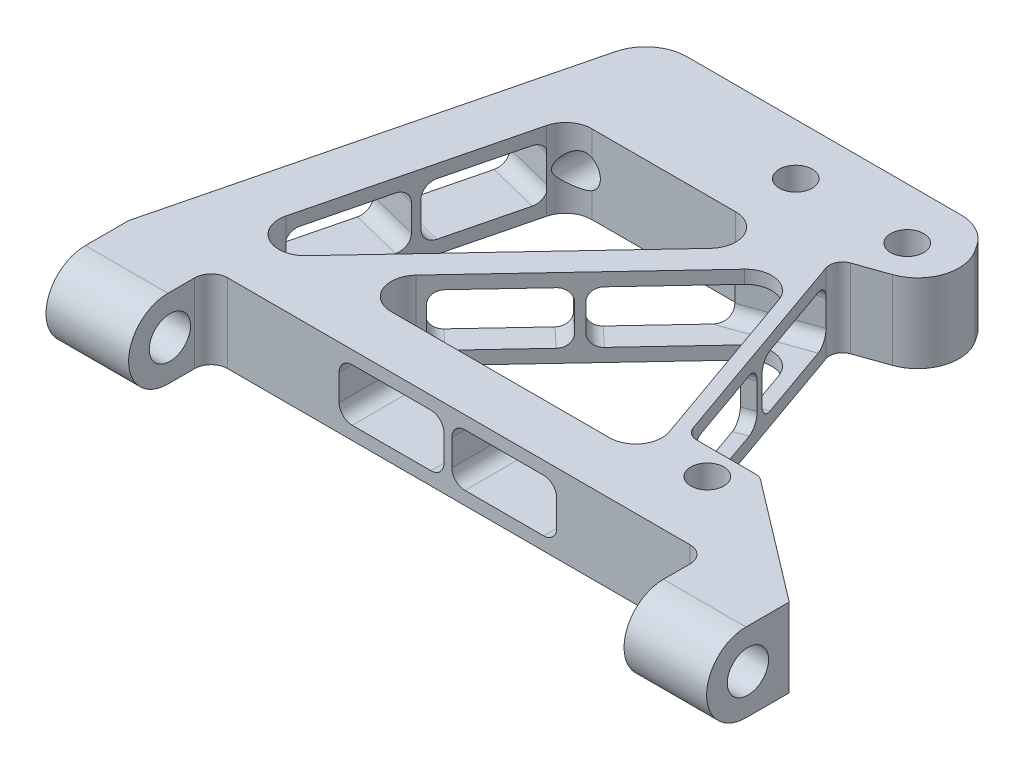
SolidWorks part; units mm, degrees
material "6061-T6 (SS)"
ref_plane "Front Plane" through (0, 0, 0) normal (0, 0, 1) x (1, 0, 0)
ref_plane "Top Plane" through (0, 0, 0) normal (0, 1, 0) x (1, 0, 0)
ref_plane "Right Plane" through (0, 0, 0) normal (1, 0, 0) x (0, 0, -1)
sketch "Sketch1" plane through (0, 0, 0) normal (0, 1, 0) x (1, 0, 0)
  line L3 (0, -122) -> (20, -122)
  line L5 (20, -122) -> (346.4065, -122) construction
  line L7 (140, -106) -> (140, -122)
  line L9 (140, -122) -> (160, -122)
  line L10 (136, -102) -> (24, -102)
  line L12 (20, -106) -> (20, -122)
  line L16 (160, -122) -> (160, -84)
  line L20 (24, -102) -> (0, -102) construction
  line L21 (0, 0) -> (0, -102) construction
  line L22 (0, -102) -> (25.4, 0)
  line L23 (0, -102) -> (0, -122)
  line L24 (105, 0) -> (25.4, 0)
  line L25 (105, 0) -> (160, -84)
  line L36 (-14.04, -12.4142) -> (141.5, -12.4142) construction
  line L41 (0, 0) -> (25.4, 0) construction
  line L42 (-24.6497, -112) -> (196.247, -112) construction
  arc A3 (136, -102) -> (140, -106) centre (136, -106) cw
  arc A4 (24, -102) -> (20, -106) centre (24, -106) ccw
  circle A5 centre (99, -12.4142) radius 4
  circle A6 centre (72, -12.4142) radius 4
  point P19 (34.925, 30)
  point P22 (140, -102)
  point P25 (20, -102)
  point P30 (25.4, 0)
  point P33 (0, 0)
  dimension "D7" = 105
  dimension "D9" = 112
  dimension "D10" = 4
  dimension "D11" = 10
  dimension "D12" = 8
  dimension "D13" = 27
  dimension "D15" = 12.4142
  dimension "D2" = 25.4
  dimension "D3" = 20
  dimension "D4" = 140
  dimension "D5" = 20
  dimension "D6" = 34.925
  dimension "D8" = 30
  dimension "D14" = 38
  dimension "D16" = 72
extrude "Boss-Extrude1" add sketch "Sketch1" along normal blind 19.05 contours L3 | A4 L10 L3 L12 | L10 A3 L7 L9 L16 | L16 L25 L24 L22 L23 L3 L12 A4 L10 A3 L7 L9 region at (76.2492, 0, 60.5513)
sketch "Sketch7" plane through (0, 0, 0) normal (0, 0, -1) x (-1, 0, 0)
  line L0 (-34.925, 9.525) -> (0, 9.525) construction
  line L3 (0, 19.05) -> (0, 0) construction
  circle A0 centre (-34.925, 9.525) radius 3.9687
  dimension "D1" = 7.9375
  dimension "D2" = 34.925
extrude "Cut-Extrude7" cut sketch "Sketch7" against normal blind 38.1
sketch "Sketch31" plane through (0, 19.05, 0) normal (0, 1, 0) x (1, 0, 0)
  line L1 (0, 0) -> (25.4, 0) construction
  line L2 (0, 0) -> (0, -102) construction
  circle A0 centre (123.7506, -85.5773) radius 4
  dimension "D1" = 8
  dimension "D2" = 85.5773
  dimension "D3" = 123.7506
extrude "Cut-Extrude18" cut sketch "Sketch31" against normal through all
fillet "Fillet6" 2 edges at (10, 19.05, 122) (10, 0, 122) type full round first side face at (123.7506, 19.05, 89.5773) second side face at (123.7506, 0, 89.5773) middle face at (10, 9.525, 122)
fillet "Fillet7" 2 edges at (150, 19.05, 122) (150, 0, 122) type full round first side face at (123.7506, 19.05, 89.5773) second side face at (123.7506, 0, 89.5773) middle face at (150, 9.525, 122)
sketch "Sketch27" plane through (0, 0, 0) normal (-1, 0, 0) x (0, 0, 1)
  line L0 (112, 0) -> (112, 19.05) construction
  line L1 (102, 0) -> (122, 0) construction
  line L2 (102, 19.05) -> (112.475, 19.05) construction
  circle A0 centre (112, 9.525) radius 5
  point P12 (112, 9.525)
  dimension "D1" = 10
extrude "Cut-Extrude16" cut sketch "Sketch27" against normal through all
sketch "Sketch28" plane through (0, 0, 0) normal (1, 0, 0) x (0, 0, -1)
  line L0 (-112, -190.4281) -> (-112, 209.4781) construction
  line L1 (-12.4142, 100.6714) -> (-112, 209.4781) construction
  line L2 (-12.4142, -81.6214) -> (-112, -190.4281) construction
  line L3 (-112, 9.525) -> (23, 9.525) construction
  line L4 (-112, 9.525) -> (-210.4838, 111.8233) construction
  line L5 (-210.4838, 111.8233) -> (-316.7444, 9.525) construction
  line L6 (-112, 9.525) -> (-316.7444, 9.525) construction
  line L7 (0, 35.7967) -> (-207.2867, 123.3896) construction
  line L8 (0, 19.05) -> (-84, 19.05) construction
  line L9 (0, 35.7967) -> (0, 19.05) construction
  line L11 (-112.475, 19.05) -> (-84, 19.05) construction
  line L12 (-92.1423, 19.05) -> (-214.5123, 100.5197) construction
  circle A1 centre (-112, 9.525) radius 135 construction
  circle A3 centre (-12.4142, 100.6714) radius 4
  circle A4 centre (-12.4142, -81.6214) radius 4
  circle A5 centre (-112, 9.525) radius 142 construction
  circle A6 centre (-210.4838, 111.8233) radius 12 construction
  point P12 (-112, 9.525)
  dimension "D1" = 135
  dimension "D4" = 8
  dimension "D6" = 142
  dimension "D9" = 24
  dimension "D2" = 147.5
  dimension "D3" = 199.9531
  dimension "D5" = 81.6214
  dimension "D7" = 147.5
  dimension "D8" = 204.7444
sketch3d "3DSketch1"
  line L0 (160, 9.525, 112) -> (0, 9.525, 112) construction
  line L1 (160, 9.525, 112) -> (140, 9.525, 112) construction
  line L2 (20, 9.525, 112) -> (0, 9.525, 112) construction
sketch "Sketch29" plane through (0, 0, 0) normal (0, -1, 0) x (1, 0, 0)
  line L0 (0, 12.4142) -> (133.1578, 12.4142) construction
  line L1 (0, 8.4142) -> (0, 16.4142) construction
sketch "Sketch30" plane through (0, 0, 0) normal (0, -1, 0) x (1, 0, 0)
  circle A0 centre (72, 12.4142) radius 4 construction
  circle A1 centre (99, 12.4142) radius 4 construction
  circle A2 centre (72, 12.4142) radius 4
  circle A3 centre (99, 12.4142) radius 4
extrude "Cut-Extrude17" cut sketch "Sketch30" against normal through all
sketch "Sketch32" plane through (0, 19.05, 0) normal (0, 1, 0) x (1, 0, 0)
  line L10 (140, -106) -> (140, -112.475)
  line L11 (140, -112.475) -> (160, -112.475)
  line L12 (160, -112.475) -> (160, -84)
  line L13 (160, -84) -> (105, 0)
  line L14 (105, 0) -> (25.4, 0)
  line L15 (25.4, 0) -> (0, -102)
  line L16 (0, -102) -> (0, -112.475)
  line L17 (0, -112.475) -> (20, -112.475)
  line L18 (20, -112.475) -> (20, -106)
  line L19 (24, -102) -> (136, -102)
  line L20 (140, -106) -> (140, -112.475)
  line L21 (140, -112.475) -> (160, -112.475)
  line L22 (160, -112.475) -> (160, -84)
  line L23 (160, -84) -> (105, 0)
  line L24 (105, 0) -> (25.4, 0)
  line L25 (25.4, 0) -> (0, -102)
  line L26 (0, -102) -> (0, -112.475)
  line L27 (0, -112.475) -> (20, -112.475)
  line L28 (20, -112.475) -> (20, -106)
  line L29 (24, -102) -> (136, -102)
  line L30 (30.6562, -31.4499) -> (18.0779, -81.961)
  line L31 (36.818, -26.6343) -> (71.6779, -26.6343)
  line L33 (95.3627, -39.863) -> (109.7799, -80.8426)
  line L34 (112.7553, -89.3) -> (50.8861, -89.3)
  line L35 (50.8861, -89.3) -> (112.7553, -89.3)
  line L36 (50.8861, -89.3) -> (112.7553, -89.3)
  line L37 (76.3067, -37.3314) -> (28.8685, -87.8425)
  line L38 (84.7439, -37.6233) -> (46.2574, -78.6029)
  line L39 (50.8861, -89.3) -> (103.7898, -89.3)
  arc A2 (24, -102) -> (20, -106) centre (24, -106) ccw
  arc A3 (140, -106) -> (136, -102) centre (136, -106) ccw
  arc A4 (24, -102) -> (20, -106) centre (24, -106) ccw
  arc A5 (140, -106) -> (136, -102) centre (136, -106) ccw
  arc A6 (109.7799, -80.8426) -> (103.7898, -89.3) centre (103.7898, -82.95) cw
  arc A7 (95.3627, -39.863) -> (84.7439, -37.6233) centre (89.3726, -41.9704) ccw
  arc A8 (46.2574, -78.6029) -> (50.8861, -89.3) centre (50.8861, -82.95) ccw
  arc A9 (28.8685, -87.8425) -> (18.0779, -81.961) centre (24.2398, -83.4954) cw
  arc A10 (30.6562, -31.4499) -> (36.818, -26.6343) centre (36.818, -32.9843) cw
  arc A11 (71.6779, -26.6343) -> (76.3067, -37.3314) centre (71.6779, -32.9843) cw
  point P6 (24, -89.3)
  point P8 (136, -89.3)
  point P21 (35.3253, -12.7)
  point P23 (15.7005, -91.5084)
  dimension "D2" = 6.35
  dimension "D3" = 12.7
  dimension "D1" = 0
extrude "Cut-Extrude19" cut sketch "Sketch32" against normal through all contours A11 L31 A10 L30 A9 L37 | L38 A8 L36 A6 L33 A7 region at (43.9152, 19.05, 51.4757) region at (80.7145, 19.05, 69.4296)
sketch "Sketch33" plane through (0, 19.05, 0) normal (0, 1, 0) x (1, 0, 0)
  line L0 (160, -102) -> (130.9529, -79.8765)
  line L1 (160, -112.475) -> (160, -84) construction
  line L2 (129.0292, -79.2273) -> (114.8388, -79.2273)
  line L3 (111.8437, -77.106) -> (94.3912, -27.4986)
  line L4 (96.3325, -23.4499) -> (115.8566, -16.581)
  line L5 (105, 0) -> (160, -84) construction
  line L6 (95.3627, -39.863) -> (109.7799, -80.8426) construction
  line L7 (136, -102) -> (160, -102) construction
  line L8 (115.8566, -16.581) -> (160, -84)
  line L9 (160, -84) -> (160, -102)
  circle A0 centre (123.7506, -85.5773) radius 4 construction
  circle A1 centre (99, -12.4142) radius 4 construction
  arc A2 (130.9529, -79.8765) -> (129.0292, -79.2273) centre (129.0292, -82.4023) ccw
  arc A3 (114.8388, -79.2273) -> (111.8437, -77.106) centre (114.8388, -76.0523) cw
  arc A4 (94.3912, -27.4986) -> (96.3325, -23.4499) centre (97.3862, -26.4449) cw
  point P21 (130.1006, -79.2273)
  dimension "D2" = 6.35
  dimension "D3" = 9.525
  dimension "D5" = 3.175
  dimension "D1" = 6.35
  dimension "D4" = 90
extrude "Cut-Extrude20" cut sketch "Sketch33" against normal blind 44
fillet "Fillet8" radius 10 3 edges at (115.8566, 9.525, 16.581) (25.4, 9.525, 0) (105, 9.525, 0)
sketch "Sketch34" plane through (36.2405, 0, 9.0246) normal (0.9704, 0, 0.2416) x (0.2416, 0, -0.9704)
  line L0 (-45.0095, 3.175) -> (-25.9595, 3.175)
  line L1 (-48.1845, 12.7) -> (-48.1845, 6.35)
  line L2 (-50.0895, 12.7) -> (-50.0895, 6.35)
  line L3 (-53.2645, 15.875) -> (-72.3145, 15.875)
  line L4 (-72.3145, 3.175) -> (-53.2645, 3.175)
  line L5 (-25.9595, 15.875) -> (-45.0095, 15.875)
  line L6 (-22.7845, 12.7) -> (-22.7845, 6.35)
  line L7 (-75.4895, 12.7) -> (-75.4895, 6.35)
  line L8 (-49.137, 19.05) -> (-49.137, 0) construction
  line L9 (-23.1101, 19.05) -> (-75.1638, 19.05) construction
  line L10 (-23.1101, 0) -> (-75.1638, 0) construction
  line L11 (-50.0895, 9.525) -> (-48.1845, 9.525) construction
  arc A0 (-22.7845, 6.35) -> (-25.9595, 3.175) centre (-25.9595, 6.35) cw
  arc A1 (-22.7845, 12.7) -> (-25.9595, 15.875) centre (-25.9595, 12.7) ccw
  arc A2 (-48.1845, 12.7) -> (-45.0095, 15.875) centre (-45.0095, 12.7) cw
  arc A3 (-48.1845, 6.35) -> (-45.0095, 3.175) centre (-45.0095, 6.35) ccw
  arc A4 (-50.0895, 6.35) -> (-53.2645, 3.175) centre (-53.2645, 6.35) cw
  arc A5 (-50.0895, 12.7) -> (-53.2645, 15.875) centre (-53.2645, 12.7) ccw
  arc A6 (-75.4895, 12.7) -> (-72.3145, 15.875) centre (-72.3145, 12.7) cw
  arc A7 (-75.4895, 6.35) -> (-72.3145, 3.175) centre (-72.3145, 6.35) ccw
  dimension "D1" = 25.4
  dimension "D2" = 25.4
  dimension "D3" = 1.905
extrude "Cut-Extrude21" cut sketch "Sketch34" against normal up to next
sketch "Sketch35" plane through (63.8027, 0, 59.9211) normal (0.7289, 0, 0.6846) x (0.6846, 0, -0.7289)
  line L0 (6.6078, 3.175) -> (25.6578, 3.175)
  line L1 (3.4328, 12.7) -> (3.4328, 6.35)
  line L2 (1.5278, 12.7) -> (1.5278, 6.35)
  line L3 (-1.6472, 15.875) -> (-20.6972, 15.875)
  line L4 (-20.6972, 3.175) -> (-1.6472, 3.175)
  line L5 (25.6578, 15.875) -> (6.6078, 15.875)
  line L6 (28.8328, 12.7) -> (28.8328, 6.35)
  line L7 (-23.8722, 12.7) -> (-23.8722, 6.35)
  line L8 (2.4803, 19.05) -> (2.4803, 0) construction
  line L9 (1.5278, 9.525) -> (3.4328, 9.525) construction
  line L10 (2.4803, 19.05) -> (2.4803, 0) construction
  line L11 (30.5896, 19.05) -> (-25.629, 19.05) construction
  line L12 (30.5896, 0) -> (-25.629, 0) construction
  arc A0 (28.8328, 6.35) -> (25.6578, 3.175) centre (25.6578, 6.35) cw
  arc A1 (28.8328, 12.7) -> (25.6578, 15.875) centre (25.6578, 12.7) ccw
  arc A2 (3.4328, 12.7) -> (6.6078, 15.875) centre (6.6078, 12.7) cw
  arc A3 (3.4328, 6.35) -> (6.6078, 3.175) centre (6.6078, 6.35) ccw
  arc A4 (1.5278, 6.35) -> (-1.6472, 3.175) centre (-1.6472, 6.35) cw
  arc A5 (1.5278, 12.7) -> (-1.6472, 15.875) centre (-1.6472, 12.7) ccw
  arc A6 (-23.8722, 12.7) -> (-20.6972, 15.875) centre (-20.6972, 12.7) cw
  arc A7 (-23.8722, 6.35) -> (-20.6972, 3.175) centre (-20.6972, 6.35) ccw
  dimension "D1" = 25.4
  dimension "D2" = 25.4
  dimension "D3" = 1.905
extrude "Cut-Extrude22" cut sketch "Sketch35" against normal up to next
sketch "Sketch36" plane through (0, 0, 89.3) normal (0, 0, -1) x (-1, 0, 0)
  line L0 (-73.2105, 3.2023) -> (-54.1605, 3.2023)
  line L1 (-76.3855, 12.7273) -> (-76.3855, 6.3773)
  line L2 (-78.2905, 12.7273) -> (-78.2905, 6.3773)
  line L3 (-81.4655, 15.9023) -> (-100.5155, 15.9023)
  line L4 (-100.5155, 3.2023) -> (-81.4655, 3.2023)
  line L5 (-54.1605, 15.9023) -> (-73.2105, 15.9023)
  line L6 (-50.9855, 12.7273) -> (-50.9855, 6.3773)
  line L7 (-103.6905, 12.7273) -> (-103.6905, 6.3773)
  line L8 (-77.338, 19.0773) -> (-77.338, 0.0273) construction
  line L9 (-78.2905, 9.5523) -> (-76.3855, 9.5523) construction
  line L10 (-77.338, 19.05) -> (-77.338, 0) construction
  line L11 (-103.7898, 19.05) -> (-50.8861, 19.05) construction
  line L12 (-103.7898, 0) -> (-50.8861, 0) construction
  arc A0 (-50.9855, 6.3773) -> (-54.1605, 3.2023) centre (-54.1605, 6.3773) cw
  arc A1 (-50.9855, 12.7273) -> (-54.1605, 15.9023) centre (-54.1605, 12.7273) ccw
  arc A2 (-76.3855, 12.7273) -> (-73.2105, 15.9023) centre (-73.2105, 12.7273) cw
  arc A3 (-76.3855, 6.3773) -> (-73.2105, 3.2023) centre (-73.2105, 6.3773) ccw
  arc A4 (-78.2905, 6.3773) -> (-81.4655, 3.2023) centre (-81.4655, 6.3773) cw
  arc A5 (-78.2905, 12.7273) -> (-81.4655, 15.9023) centre (-81.4655, 12.7273) ccw
  arc A6 (-103.6905, 12.7273) -> (-100.5155, 15.9023) centre (-100.5155, 12.7273) cw
  arc A7 (-103.6905, 6.3773) -> (-100.5155, 3.2023) centre (-100.5155, 6.3773) ccw
  dimension "D1" = 25.4
  dimension "D2" = 25.4
  dimension "D3" = 1.905
extrude "Cut-Extrude23" cut sketch "Sketch36" against normal up to next
sketch "Sketch37" plane through (75.386, 0, -26.5218) normal (0.9433, 0, -0.3319) x (-0.3319, 0, -0.9433)
  line L0 (-79.4326, 3.175) -> (-60.3826, 3.175)
  line L1 (-82.6076, 12.7) -> (-82.6076, 6.35)
  line L2 (-84.5126, 12.7) -> (-84.5126, 6.35)
  line L3 (-87.6876, 15.875) -> (-106.7376, 15.875)
  line L4 (-106.7376, 3.175) -> (-87.6876, 3.175)
  line L5 (-60.3826, 15.875) -> (-79.4326, 15.875)
  line L6 (-57.2076, 12.7) -> (-57.2076, 6.35)
  line L7 (-109.9126, 12.7) -> (-109.9126, 6.35)
  line L8 (-83.5601, 19.05) -> (-83.5601, 0) construction
  line L9 (-84.5126, 9.525) -> (-82.6076, 9.525) construction
  line L10 (-83.5601, 19.05) -> (-83.5601, 0) construction
  line L12 (-57.2661, 19.05) -> (-109.854, 19.05) construction
  line L13 (-57.2661, 0) -> (-109.854, 0) construction
  line L14 (-109.854, 9.525) -> (-57.2661, 9.525) construction
  line L15 (-109.854, 0) -> (-109.854, 19.05) construction
  line L16 (-57.2661, 0) -> (-57.2661, 19.05) construction
  arc A0 (-57.2076, 6.35) -> (-60.3826, 3.175) centre (-60.3826, 6.35) cw
  arc A1 (-57.2076, 12.7) -> (-60.3826, 15.875) centre (-60.3826, 12.7) ccw
  arc A2 (-82.6076, 12.7) -> (-79.4326, 15.875) centre (-79.4326, 12.7) cw
  arc A3 (-82.6076, 6.35) -> (-79.4326, 3.175) centre (-79.4326, 6.35) ccw
  arc A4 (-84.5126, 6.35) -> (-87.6876, 3.175) centre (-87.6876, 6.35) cw
  arc A5 (-84.5126, 12.7) -> (-87.6876, 15.875) centre (-87.6876, 12.7) ccw
  arc A6 (-109.9126, 12.7) -> (-106.7376, 15.875) centre (-106.7376, 12.7) cw
  arc A7 (-109.9126, 6.35) -> (-106.7376, 3.175) centre (-106.7376, 6.35) ccw
  dimension "D1" = 25.4
  dimension "D2" = 25.4
  dimension "D3" = 1.905
extrude "Cut-Extrude24" cut sketch "Sketch37" against normal up to next
